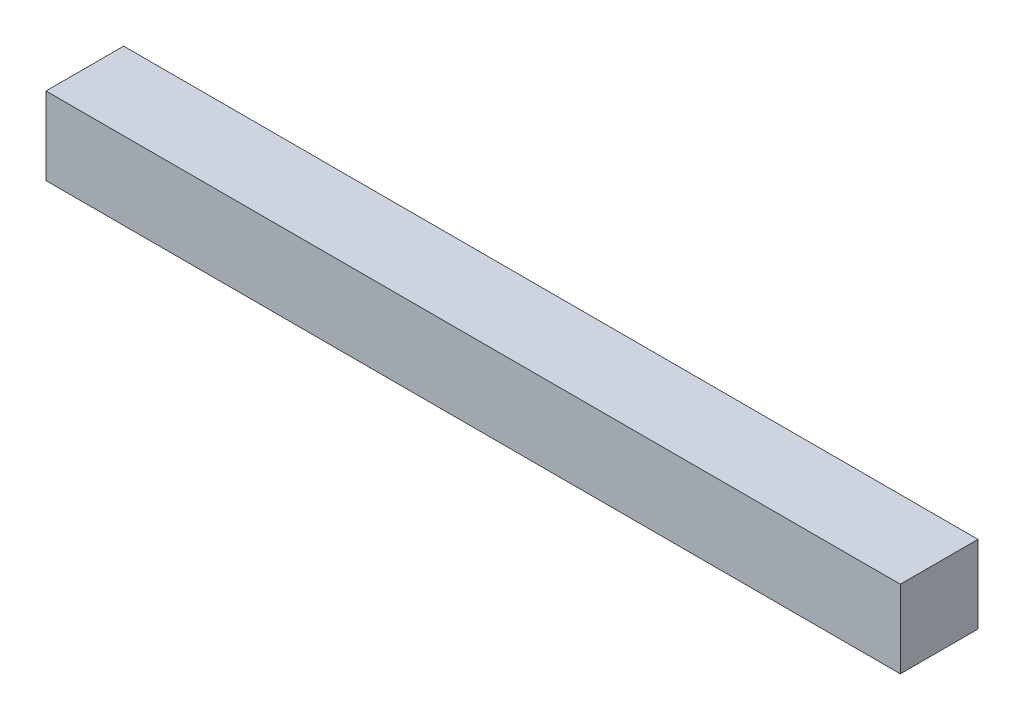
SolidWorks part; units mm, degrees
ref_plane "正面" through (0, 0, 0) normal (0, 0, 1) x (1, 0, 0)
ref_plane "平面" through (0, 0, 0) normal (0, 1, 0) x (1, 0, 0)
ref_plane "右側面" through (0, 0, 0) normal (1, 0, 0) x (0, 0, -1)
sketch "ｽｹｯﾁ1" plane through (0, 0, 0) normal (0, 1, 0) x (1, 0, 0)
  line L1 (-55, -5) -> (55, -5)
  line L2 (-55, -5) -> (-55, 5)
  line L3 (-55, 5) -> (55, 5)
  line L4 (55, -5) -> (55, 5)
  line L5 (-55, -5) -> (55, 5) construction
  line L6 (-55, 5) -> (55, -5) construction
  point P0 (0, 0)
  dimension "D1" = 110
  dimension "D2" = 10
extrude "ﾎﾞｽ - 押し出し1" add sketch "ｽｹｯﾁ1" along normal blind 10
